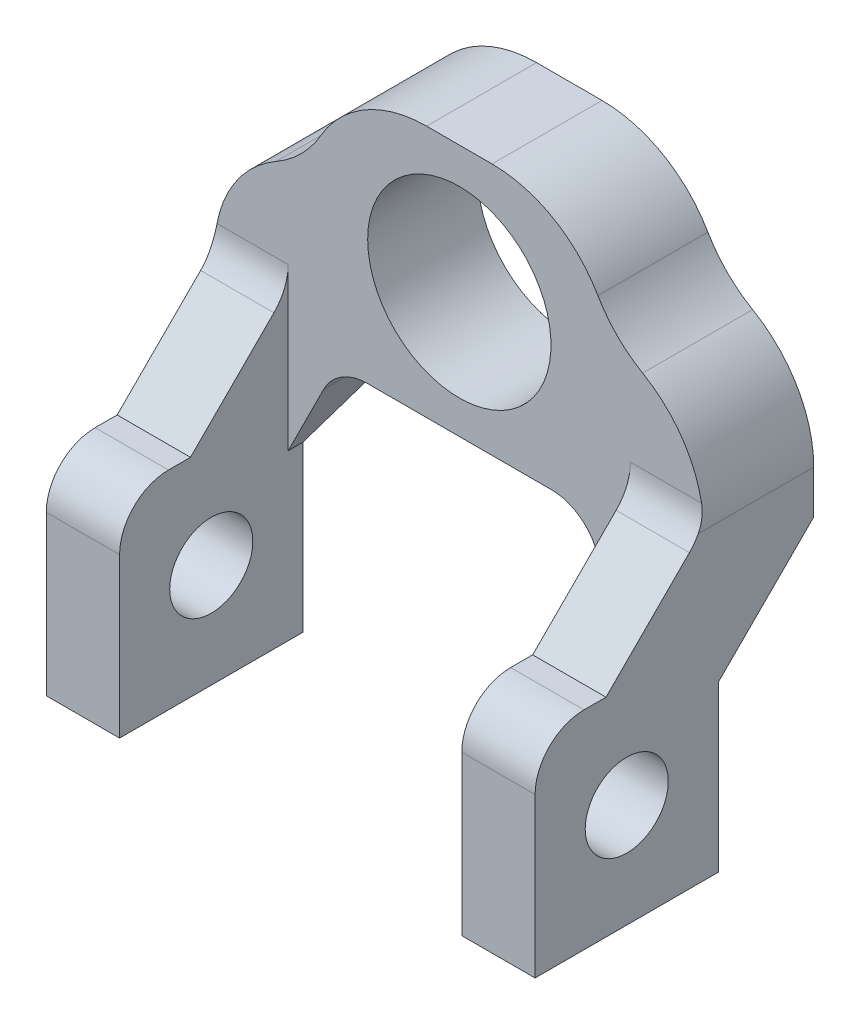
SolidWorks part; units mm, degrees
ref_plane "Alzado" through (0, 0, 0) normal (0, 0, 1) x (1, 0, 0)
ref_plane "Planta" through (0, 0, 0) normal (0, 1, 0) x (1, 0, 0)
ref_plane "Vista lateral" through (0, 0, 0) normal (1, 0, 0) x (0, 0, -1)
sketch "Croquis1" plane through (0, 0, 0) normal (1, 0, 0) x (0, 0, -1)
  line L0 (5.4, 16.814) -> (5.4, -4.8468) construction
  line L1 (-3.75, 4.25) -> (-0.85, 4.25)
  line L2 (-3.75, 4.25) -> (-3.75, -4.25)
  line L3 (-3.75, -4.25) -> (3.75, -4.25)
  line L4 (3.75, 2.486) -> (3.75, -4.25)
  line L5 (-3.75, 4.25) -> (3.75, -4.25) construction
  line L6 (-3.75, -4.25) -> (3.75, 4.25) construction
  line L8 (3.15, 8.25) -> (3.15, 16.814)
  line L9 (3.15, 16.814) -> (7.65, 16.814)
  line L10 (7.65, 6.386) -> (7.65, 16.814)
  line L12 (-0.85, 4.25) -> (3.15, 8.25)
  line L13 (-0.85, 4.25) -> (3.75, 4.25) construction
  line L14 (3.75, 4.25) -> (3.75, 2.486) construction
  line L15 (3.75, 2.486) -> (7.65, 6.386)
  circle A0 centre (5.4, -29) radius 37.1 construction
  circle A1 centre (5.4, -29) radius 24.75 construction
  circle A2 centre (5.4, 11.6) radius 3.5 construction
  point P0 (0, 0)
  point P6 (3.15, 4.25)
  point P16 (7.65, 11.6)
  dimension "D6" = 74.2
  dimension "D7" = 49.5
  dimension "D8" = 7
  dimension "D1" = 4.5
  dimension "D2" = 7.5
  dimension "D3" = 6.9
  dimension "D4" = 8.5
  dimension "D5" = 4.5
extrude "Saliente-Extruir1" add sketch "Croquis1" along normal blind 20
sketch "Croquis2" plane through (0, -4.25, 0) normal (0, -1, 0) x (1, 0, 0)
  line L0 (20, 3.75) -> (0, 3.75) construction
  line L1 (3, 3.75) -> (17, 3.75)
  line L2 (3, 3.75) -> (3, -3.75)
  line L3 (3, -3.75) -> (17, -3.75)
  line L4 (17, 3.75) -> (17, -3.75)
  line L5 (20, -3.75) -> (0, -3.75) construction
  line L6 (0, 0) -> (20, 0) construction
  line L7 (20, 3.75) -> (20, -3.75) construction
  line L8 (10, 0) -> (10, 5.8604) construction
  point P14 (10, 0)
  point P15 (10, 3.75)
  point P17 (10, -3.75)
  dimension "D1" = 14
extrude "Cortar-Extruir1" cut sketch "Croquis2" against normal up to vertex (6.736 mm away) up to point (0, 2.486, -3.75)
sketch "Croquis3" plane through (0, 0, 0) normal (-1, 0, 0) x (0, 0, 1)
  circle A0 centre (0, 0) radius 1.7
  dimension "D1" = 3.4
extrude "Cortar-Extruir2" cut sketch "Croquis3" against normal up to surface (20 mm away) up to face at (20, 5.6389, -2.3056)
sketch "Croquis5" plane through (0, 0, -3.15) normal (0, 0, 1) x (1, 0, 0)
  line L0 (20, 8.25) -> (0, 8.25) construction
  line L1 (3, 2.486) -> (17, 2.486)
  line L2 (3, 2.486) -> (3, 8.25)
  line L3 (3, 8.25) -> (17, 8.25)
  line L4 (17, 2.486) -> (17, 8.25)
  line L5 (17, 2.486) -> (17, -4.25) construction
extrude "Cortar-Extruir4" cut sketch "Croquis5" along normal blind 10
sketch "Croquis4" plane through (0, 0, -7.65) normal (0, 0, -1) x (-1, 0, 0)
  line L0 (-20, 11.814) -> (-15, 11.814)
  line L2 (-15, 11.814) -> (-15, 16.814)
  line L3 (-20, 16.814) -> (0, 16.814) construction
  line L4 (-15, 16.814) -> (-20, 16.814)
  line L5 (-20, 16.814) -> (-20, 11.814)
  line L6 (-10, 14.7) -> (-10, 9.5322) construction
  line L7 (-5, 16.814) -> (0, 16.814)
  line L8 (0, 16.814) -> (0, 11.814)
  line L9 (0, 11.814) -> (-5, 11.814)
  line L10 (-5, 11.814) -> (-5, 16.814)
  line L11 (0, 11.6) -> (-10, 11.6) construction
  line L12 (0, 6.386) -> (0, 16.814) construction
  line L15 (-15, 6.486) -> (-5, 6.486)
  line L20 (-15, 6.486) -> (-17, 2.486)
  line L21 (-17, 2.486) -> (-3, 2.486)
  line L22 (-3, 2.486) -> (-5, 6.486)
  circle A1 centre (-10, 11.6) radius 3.75
  point P24 (-10, 6.486)
  dimension "D1" = 7.5
  dimension "D2" = 5
  dimension "D3" = 5
  dimension "D4" = 4
  dimension "D5" = 10
extrude "Cortar-Extruir3" cut sketch "Croquis4" against normal up to surface (4.5 mm away) up to face at (10, 8.95, -3.15)
fillet "Redondeo1" radius 5 2 edges at (5, 11.814, -5.4) (15, 11.814, -5.4)
fillet "Redondeo2" radius 5 4 edges at (15, 16.814, -5.4) (5, 16.814, -5.4) (20, 11.814, -5.4) (0, 11.814, -5.4)
fillet "Redondeo3" radius 2 6 edges at (15, 6.486, -5.4) (5, 6.486, -5.4) (1.5005, 8.25, -3.15) (18.4995, 8.25, -3.15) (18.5, 4.25, 3.75) (1.5, 4.25, 3.75)
